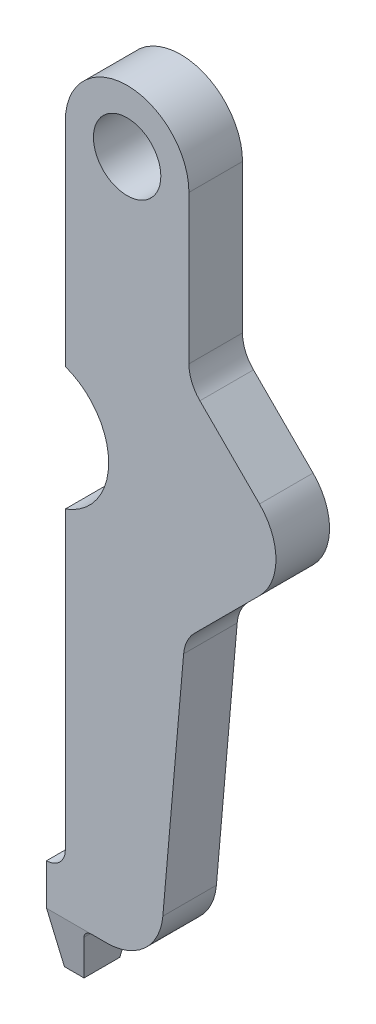
SolidWorks part; units mm, degrees
ref_plane "Front Plane" through (0, 0, 0) normal (0, 0, 1) x (1, 0, 0)
ref_plane "Top Plane" through (0, 0, 0) normal (0, 1, 0) x (1, 0, 0)
ref_plane "Right Plane" through (0, 0, 0) normal (1, 0, 0) x (0, 0, -1)
other "Configuration Table"
sketch "Sketch1" plane through (0, 0, 0) normal (0, 0, 1) x (1, 0, 0)
  line L0 (0, 0) -> (0, 44.069)
  line L1 (8.382, 44.069) -> (8.382, 32.9498)
  line L2 (8.1028, 17.7123) -> (15.8611, 25.4706)
  line L3 (15.8611, 25.4706) -> (8.382, 32.9498)
  line L4 (8.1028, 17.7123) -> (6.5532, 0)
  line L5 (6.5532, 0) -> (0, 0)
  line L6 (-11.7068, 44.069) -> (19.8228, 44.069) construction
  line L7 (4.191, 44.069) -> (4.191, 62.3822) construction
  line L8 (17.1955, 25.4706) -> (-26.9206, 25.4706) construction
  arc A0 (8.382, 44.069) -> (0, 44.069) centre (4.191, 44.069) ccw
  dimension "D3" = 4.191
  dimension "D1" = 48.26
  dimension "D2" = 17.78
  dimension "D4" = 8.382
  dimension "D5" = 6.5532
  dimension "D7" = 45
  dimension "D8" = 15.24
  dimension "D9" = 85
extrude "Extrude1" add sketch "Sketch1" along normal mid plane 3.6322
fillet "Fillet1" radius 3.81 1 edges at (15.8611, 25.4706, 0)
fillet "Fillet2" radius 2.54 2 edges at (8.1028, 17.7123, 0) (8.382, 32.9498, 0)
sketch "Sketch2" plane through (0, 0, 0) normal (0, -1, 0) x (1, 0, 0)
  line L0 (0, -1.8161) -> (6.5532, -1.8161) construction
  line L1 (6.5532, 1.8161) -> (-1.27, 1.8161)
  line L2 (6.5532, 1.8161) -> (6.5532, -1.8161)
  line L3 (6.5532, -1.8161) -> (-1.27, -1.8161)
  line L4 (-1.27, 1.8161) -> (-1.27, -1.8161)
  line L5 (0, 1.8161) -> (0, -1.8161) construction
  dimension "D1" = 1.27
extrude "Extrude2" add sketch "Sketch2" along normal blind 2.794
sketch "Sketch3" plane through (0, -2.794, 0) normal (0, -1, 0) x (1, 0, 0)
  line L0 (-1.27, -1.8161) -> (6.5532, -1.8161) construction
  line L1 (-1.27, 1.8161) -> (1.27, 1.8161)
  line L2 (-1.27, 1.8161) -> (-1.27, -1.8161)
  line L3 (-1.27, -1.8161) -> (1.27, -1.8161)
  line L4 (1.27, 1.8161) -> (1.27, -1.8161)
  dimension "D1" = 2.54
extrude "Extrude3" add sketch "Sketch3" along normal blind 3.429 draft 10
fillet "Fillet3" radius 3.81 1 edges at (6.5532, -2.794, 0)
fillet "Fillet4" radius 0.635 1 edges
fillet "Fillet5" radius 1.27 1 edges
sketch "Sketch4" plane through (0, 0, 1.8161) normal (0, 0, 1) x (1, 0, 0)
  circle A0 centre (4.191, 44.069) radius 2.286
  dimension "D1" = 4.572
extrude "Cut-Extrude1" cut sketch "Sketch4" against normal through all
sketch "Sketch5" plane through (0, 0, 0) normal (0, 0, 1) x (1, 0, 0)
  line L0 (14.283, 25.4706) -> (-18.8764, 25.4706) construction
  arc A0 (13.1671, 22.7766) -> (13.1671, 28.1647) centre (10.473, 25.4706) ccw construction
  circle A1 centre (-1.5046, 25.4706) radius 4.445
  dimension "D1" = 8.89
extrude "Cut-Extrude2" cut sketch "Sketch5" against normal through all and the other way through all
